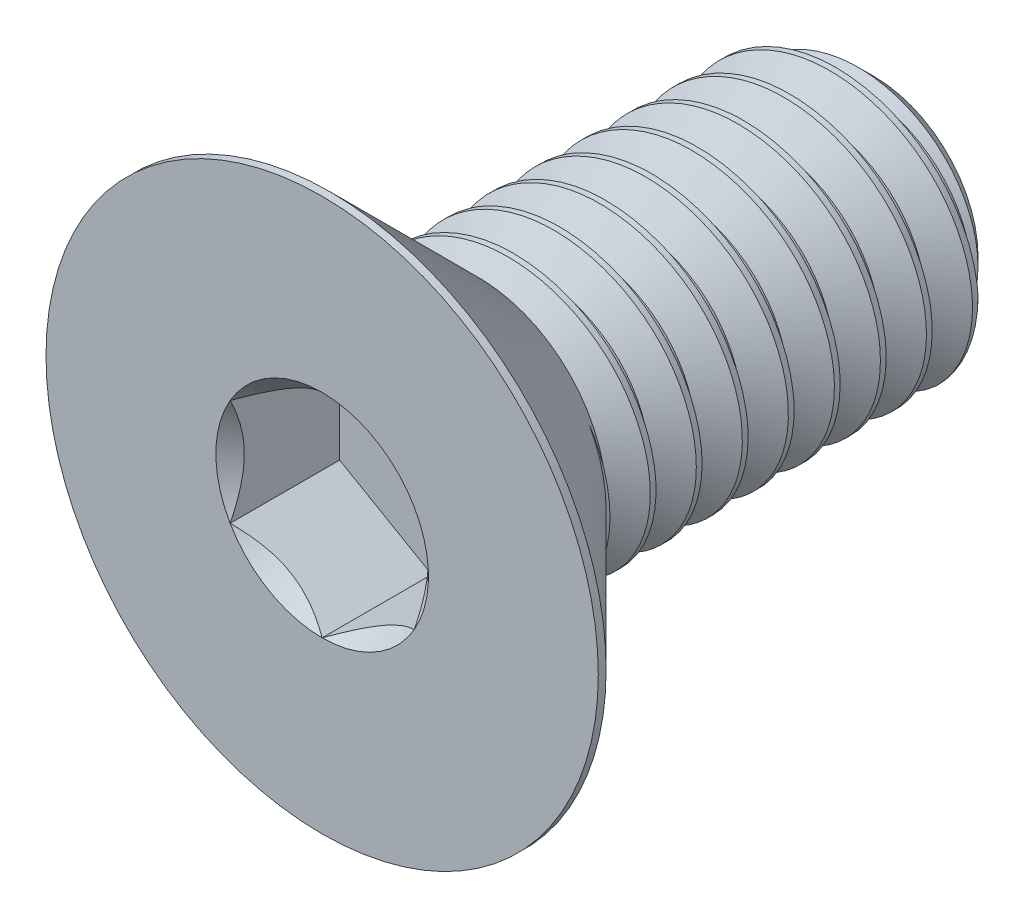
SolidWorks part; units mm, degrees
material "AISI 304"
ref_plane "Front" through (0, 0, 0) normal (0, 0, 1) x (1, 0, 0)
ref_plane "Top" through (0, 0, 0) normal (0, 1, 0) x (1, 0, 0)
ref_plane "Right" through (0, 0, 0) normal (1, 0, 0) x (0, 0, -1)
sketch "Sketch11" plane through (0, 0, 0) normal (1, 0, 0) x (0, 0, -1)
  line L0 (-3, 3) -> (3, 3) construction
  line L5 (-3, 3) -> (-3, -3) construction
  line L6 (3, 1.5) -> (3, -1.5) construction
  line L7 (-2.99, 1) -> (-2.99, -1) construction
  line L8 (2.9688, 1.5541) -> (3.4688, 1.5541) construction
  line L9 (3.4688, 1.5541) -> (3.2188, 1.1211) construction
  line L10 (3.2188, 1.1211) -> (2.9688, 1.5541) construction
  line L11 (3.1875, 1.1752) -> (3.25, 1.1752) construction
  line L12 (3.2188, 1.1752) -> (3.2188, 1.1211) construction
  line L13 (2.9844, 1.5271) -> (3.4531, 1.5271) construction
  line L14 (3.2188, 1.5541) -> (3.2188, 1.5) construction
  line L15 (3, 1.5) -> (3.4375, 1.5) construction
  line L17 (-2.915, 3) -> (0.085, 0) construction
  line L18 (0.085, 0) -> (-2.915, -3) construction
  point P3 (-1.3, 3)
  point P8 (0, 3)
  point P21 (3.2188, 1.5271)
  point P26 (-3, 0)
  point P28 (-2.99, 0)
  point P29 (3, 0)
  dimension "D1" = 0.0625
  dimension "D2" = 0.01
  dimension "D3" = 0.085
  dimension "Countersink Angle" = 90
sketch "Sketch1" plane through (0, 0, 0) normal (1, 0, 0) x (0, 0, -1)
  line L2 (-1.3, 1.5) -> (3, 1.5)
  line L3 (3, 1.5) -> (3, 0)
  line L4 (-1.81, 1.5) -> (-1.81, 0)
  line L5 (-1.3, 1.5) -> (-1.81, 1.5)
  line L6 (-3, 3) -> (-3, -3) construction
  line L7 (3, 1.5) -> (3, -1.5) construction
  line L8 (-1.81, 0) -> (3, 0)
  dimension "D1" = 1.19
revolve "Revolve1" add sketch "Sketch1" angle 360 mid plane about L8
chamfer "Chamfer1" distance 0.375 angle 45 1 edges at (0, -1.5, -3)
sketch "Sketch7" plane through (0, 0, 0) normal (1, 0, 0) x (0, 0, -1)
  line L2 (-3, 3) -> (-2.915, 3)
  line L5 (-1.3, 1.385) -> (-1.3, 0)
  line L6 (-3, 3) -> (-3, 0)
  line L8 (-3, 3) -> (-3, -3) construction
  line L9 (-3, 0) -> (-1.3, 0)
  line L12 (-2.915, 3) -> (-1.3, 1.385)
  line L13 (-2.915, 3) -> (0.085, 0) construction
revolve "Revolve2" add sketch "Sketch7" angle 360 mid plane about L9 region at (0, 1.1696, 2.2571)
ref_plane "Plane1" through (0, 0, 1.3) normal (0, 0, 1) x (1, 0, 0)
sketch "Sketch5" plane through (0, 0, 3) normal (0, 0, 1) x (1, 0, 0)
  line L1 (1, -0.5774) -> (1, 0.5774)
  line L2 (1, 0.5774) -> (0, 1.1547)
  line L3 (0, 1.1547) -> (-1, 0.5774)
  line L4 (-1, 0.5774) -> (-1, -0.5774)
  line L5 (-1, -0.5774) -> (0, -1.1547)
  line L6 (0, -1.1547) -> (1, -0.5774)
  circle A0 centre (0, 0) radius 1 construction
extrude "Cut-Extrude2" cut sketch "Sketch5" against normal blind 1.19
sketch "Sketch6" plane through (0, 0, 3) normal (0, 0, -1) x (-1, 0, 0)
  circle A0 centre (0, 0) radius 1.1547
extrude "Cut-Extrude3" cut sketch "Sketch6" along normal blind 1.19 draft 45
sketch "Sketch12" plane through (0, 0, -3) normal (0, 0, -1) x (-1, 0, 0)
  circle A0 centre (0, 0) radius 1.5 construction
  circle A1 centre (0, 0) radius 1.5
curve "Helix/Spiral1" pitch 0.5 height 6 radius 1.5 centre (0, 0, -3) axis (0, 0, 1) start towards (0, 1, 0)
sketch "Sketch13" plane through (0, 0, 0) normal (1, 0, 0) x (0, 0, -1)
  line L0 (2.9844, 1.5271) -> (3.4531, 1.5271)
  line L1 (3.4531, 1.5271) -> (3.25, 1.1752)
  line L2 (3.25, 1.1752) -> (3.1875, 1.1752)
  line L3 (3.1875, 1.1752) -> (2.9844, 1.5271)
sweep "Cut-Sweep1" cut profiles "Sketch13" path "Helix/Spiral1" align with end faces yes
combine bodies "Combine1" operation type add bodies to combine 113 127
equation "\"D1@Chamfer1\"=\"Thread Pitch@Sketch11\" * .75"
equation "\"D1@Cut-Extrude2\"= \"Head Height@Sketch11\" * .7"
equation "\"D1@Cut-Extrude3\" = \"D1@Cut-Extrude2\""
equation "\"D1@Sketch11\"=\"Thread Pitch@Sketch11\"/8"
equation "\"D3@Sketch11\"=\"Head Height@Sketch11\"*.05"
equation "\"D4@Helix/Spiral1\"=\"Thread Pitch@Sketch11\""
equation "\"D1@Sketch1\"=\"Head Height@Sketch11\"*.7"
equation "\"D3@Helix/Spiral1\"=\"Length@Sketch11\""
